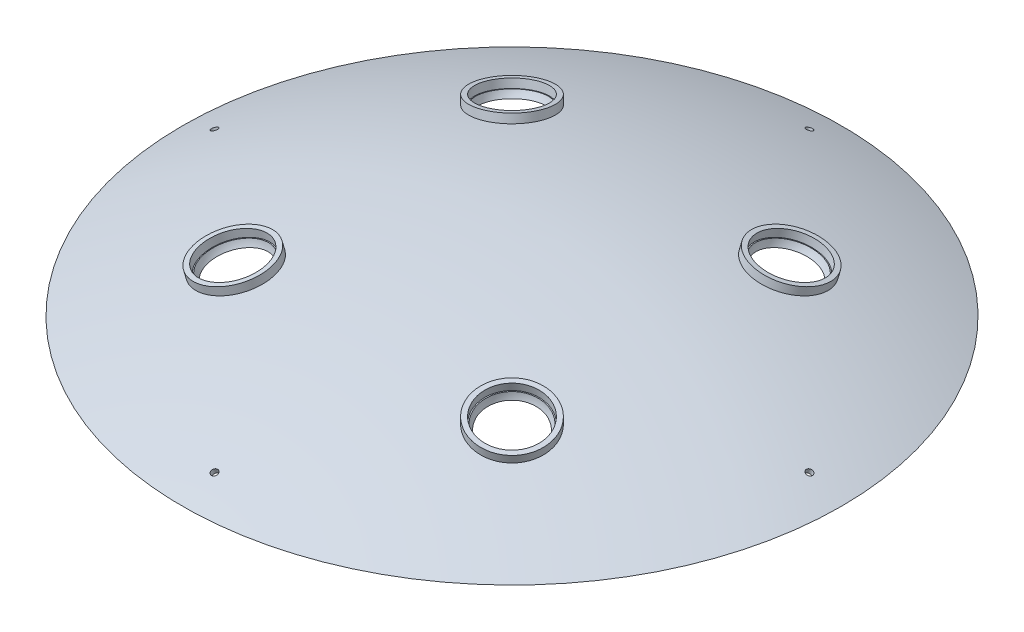
SolidWorks part; units mm, degrees
ref_plane "Front Plane" through (0, 0, 0) normal (0, 0, 1) x (1, 0, 0)
ref_plane "Top Plane" through (0, 0, 0) normal (0, 1, 0) x (1, 0, 0)
ref_plane "Right Plane" through (0, 0, 0) normal (1, 0, 0) x (0, 0, -1)
sketch "Sketch1" plane through (0, 0, 0) normal (0, 0, 1) x (1, 0, 0)
  line L0 (-150, 394.9445) -> (-150, 372.9445)
  line L1 (-150, 372.9445) -> (-100.1531, 349.7005)
  line L2 (0, 394.9445) -> (0, 544.9445)
  line L3 (0, 394.9445) -> (0, 370.6385)
  line L4 (-141.8706, 372.4638) -> (-96.4504, 351.284)
  line L9 (-100.1531, 349.7005) -> (-97.7296, 348.5704)
  line L10 (0, 370.6385) -> (0, 368.6385)
  line L12 (2, 394.9445) -> (2, 368.6305) construction
  line L13 (-152, 371.6703) -> (-100.1776, 347.5051) construction
  line L14 (-152, 394.9445) -> (-152, 371.6703) construction
  line L15 (2, 394.9445) -> (2, 546.9313) construction
  arc A0 (0, 370.6385) -> (-100.1531, 349.7005) centre (0, 120.6385) ccw
  arc A1 (0, 544.9445) -> (-150, 394.9445) centre (0, 394.9445) ccw
  arc A2 (0, 368.6385) -> (-97.7296, 348.5704) centre (0, 120.6385) ccw
  arc A4 (2, 368.6305) -> (-100.1776, 347.5051) centre (0, 120.6385) ccw construction
  arc A5 (2, 546.9313) -> (-152, 394.9445) centre (0, 394.9445) ccw construction
  point P18 (0, 0)
  dimension "D1" = 500
  dimension "D2" = 300
  dimension "D3" = 22
  dimension "D4" = 55
  dimension "D5" = 115
  dimension "D6" = 3
  dimension "D7" = 2
revolve "Revolve1" add sketch "Sketch1" angle 360 about L2 region at (-97.9016, 349.5567, 0)
sketch "Sketch3" plane through (0, 0, 0) normal (0, 0, 1) x (1, 0, 0)
  line L0 (-150, 372.9445) -> (-100.1531, 349.7005)
  line L1 (-150, 372.9445) -> (-150, 394.9445)
  line L2 (-147, 374.8557) -> (-147, 394.9445)
  line L3 (-147, 374.8557) -> (-98.8852, 352.4194)
  line L4 (-98.8852, 352.4194) -> (-96.4504, 351.284)
  line L5 (0, 120.6385) -> (-90.3797, 353.7297)
  line L6 (0.9324, 121.0001) -> (-89.4474, 354.0913)
  line L7 (1.8647, 121.3616) -> (-88.515, 354.4528)
  circle A0 centre (0, 120.6385) radius 250
  arc A1 (100.1531, 349.7005) -> (-100.1531, 349.7005) centre (0, 120.6385) ccw construction
  arc A2 (-135.5683, 330.6891) -> (-150, 394.8277) centre (0, 394.8861) ccw
  circle A3 centre (0, 120.6385) radius 247
  circle A4 centre (0.9324, 121.0001) radius 248.5
  dimension "D1" = 500
  dimension "D2" = 300
  dimension "D10" = 497
  dimension "D3" = 22
  dimension "D4" = 55
  dimension "D5" = 115
  dimension "D7" = 1.5
  dimension "D11" = 1
  dimension "D6" = 3
  dimension "D8" = 1
  dimension "D9" = 3
revolve "Cut-Revolve1" cut sketch "Sketch3" angle 360 about L5 region at (-89.6424, 353.2105, 0) region at (-89.0997, 351.8121, 0) region at (-88.1666, 352.1718, 0)
sketch "Sketch4" plane through (0, 0, 0) normal (0, 0, 1) x (1, 0, 0)
  line L0 (0, 0) -> (0, 436.9518)
pattern_circular "CirPattern2" count 4 every 90 about axis through (0, 0, 0) along (0, 1, 0) of "Cut-Revolve1"
ref_plane "Plane1" through (0, 0, 0) normal (0.7071, 0, 0.7071) x (0, 1, 0)
sketch "Sketch5" plane through (0, 0, 0) normal (0.7071, 0, 0.7071) x (0, 1, 0)
  line L0 (0, 0) -> (436.9518, 0) construction
  line L1 (356.0885, 60) -> (386.4674, 60)
  line L2 (356.0885, 60) -> (311.0583, 60)
  line L3 (363.3669, 69.2759) -> (380.5137, 73.4751)
  line L4 (363.3669, 69.2759) -> (363.0101, 70.7328)
  line L5 (120.6385, 0) -> (365.6385, 60)
  line L6 (363.0101, 70.7328) -> (359.9894, 69.9931)
  line L7 (359.9894, 69.9931) -> (360.3462, 68.5361)
  line L8 (360.3462, 68.5361) -> (363.3669, 69.2759)
  arc A0 (360.5971, 70.1419) -> (365.495, 50.4511) centre (120.6385, 0) ccw
  arc A1 (349.7005, -100.1531) -> (349.7005, 100.1531) centre (120.6385, 0) ccw construction
  circle A2 centre (365.6385, 60) radius 9.55
  arc A3 (356.0885, 60) -> (375.1885, 60) centre (365.6385, 60) ccw
  point P7 (370.6385, 0)
  point P18 (0, 0)
  dimension "D1" = 500
  dimension "D2" = 19.1
  dimension "D3" = 60
  dimension "D4" = 5
  dimension "D5" = 1.5
revolve "Cut-Revolve5" cut sketch "Sketch5" angle 360 about L2 region at (-41.8884, 359.3329, 41.8884) region at (-39.3677, 366.1605, 39.3677)
revolve "Revolve3" add sketch "Sketch5<9>" angle 360 about L5 region at (-49.239, 361.6781, 49.239)
sketch "Sketch5<9>" plane through (0, 0, 0) normal (0.7071, 0, 0.7071) x (0, 1, 0) same geometry as "Sketch5"
pattern_circular "CirPattern3" count 4 every 90 about axis through (0, 0, 0) along (0, 1, 0) of "Revolve3", "Cut-Revolve5"
